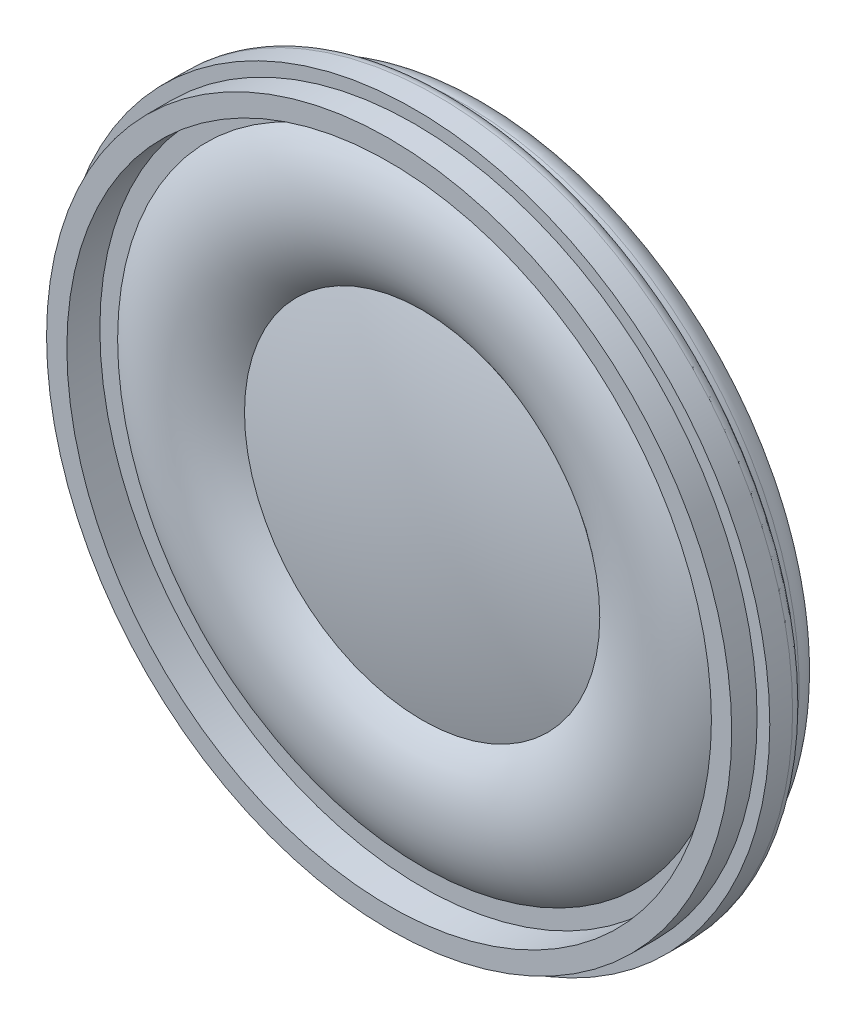
SolidWorks part; units mm, degrees
material "ABS"
ref_plane "Спереди" through (0, 0, 0) normal (0, 0, 1) x (1, 0, 0)
ref_plane "Сверху" through (0, 0, 0) normal (0, 1, 0) x (1, 0, 0)
ref_plane "Справа" through (0, 0, 0) normal (1, 0, 0) x (0, 0, -1)
ref_axis "Ось1" through (0, 0, 50) along (0, 0, -1)
sketch "Эскиз1" plane through (0, 0, 0) normal (0, 1, 0) x (1, 0, 0)
  line L0 (0, 0) -> (7.5, 0)
  line L1 (8, -0.5) -> (8, -1.5)
  line L2 (8, -1.5) -> (12.25, -1.5)
  line L3 (13.25, -2.5) -> (13.25, -3)
  line L4 (13.25, -3) -> (13.5, -3)
  line L5 (14, -3.5) -> (14, -4.4)
  line L6 (14, -4.4) -> (13.5, -4.4)
  line L7 (13.5, -4.4) -> (13.5, -5.4)
  line L8 (13.5, -5.4) -> (12.7, -5.4)
  line L9 (12.7, -5.4) -> (12.7, -4.1)
  line L10 (12.7, -4.1) -> (12, -4.1)
  line L11 (0, 0) -> (0, -5)
  line L12 (0, -5) -> (11.3788, -5) construction
  line L13 (0, 0) -> (0, -8.5626) construction
  arc A0 (0, -5) -> (7, -4.1) centre (0, 22.6722) ccw
  arc A1 (7, -4.1) -> (12, -4.1) centre (9.5, -1.0778) ccw
  arc A2 (13.25, -2.5) -> (12.25, -1.5) centre (12.25, -2.5) ccw
  arc A3 (14, -3.5) -> (13.5, -3) centre (13.5, -3.5) ccw
  arc A4 (8, -0.5) -> (7.5, 0) centre (7.5, -0.5) ccw
  point P19 (13.25, -1.5)
  point P22 (14, -3)
  point P25 (8, 0)
  dimension "D12" = 1
  dimension "D15" = 27
  dimension "D16" = 0.5
  dimension "D17" = 0.5
  dimension "D2" = 16
  dimension "D3" = 1.5
  dimension "D4" = 26.5
  dimension "D5" = 1.5
  dimension "D6" = 1.4
  dimension "D7" = 1
  dimension "D8" = 24
  dimension "D9" = 0.8
  dimension "D10" = 1.3
  dimension "D11" = 5.4
  dimension "D13" = 14
  dimension "D14" = 5
  dimension "D18" = 28
revolve "Повернуть2" add sketch "Эскиз1" angle 360 about L11
sketch "Эскиз2" plane through (0, 0, 1.5) normal (0, 0, -1) x (-1, 0, 0)
  line L0 (5.5645, -6.5899) -> (7.5, -8.882)
  line L1 (-5.5645, -6.5899) -> (-7.5, -8.882)
  line L2 (0, 0) -> (5.5645, -6.5899) construction
  line L3 (0, 0) -> (-5.5645, -6.5899) construction
  line L4 (0, -8.625) -> (0, -11.625) construction
  line L5 (0, -8) -> (0, -12.25) construction
  arc A0 (-5.5645, -6.5899) -> (5.5645, -6.5899) centre (0, 0) ccw
  arc A1 (-7.5, -8.882) -> (7.5, -8.882) centre (0, 0) ccw
  circle A2 centre (0, 0) radius 8 construction
  circle A4 centre (0, 0) radius 12.25 construction
  point P11 (0, -10.125)
  point P12 (0, -10.125)
  dimension "D1" = 3
  dimension "D2" = 15
extrude "Бобышка-Вытянуть2" add sketch "Эскиз2" along normal blind 0.4
sketch "Эскиз4" plane through (0, 0, 0) normal (0, 0, -1) x (-1, 0, 0)
  text T0 "8Ω 2W\r\n" font "Arial" height 3
  text T1 "−  +" font "Arial" height 4
extrude "Бобышка-Вытянуть3" add sketch "Эскиз4" along normal blind 0.01
